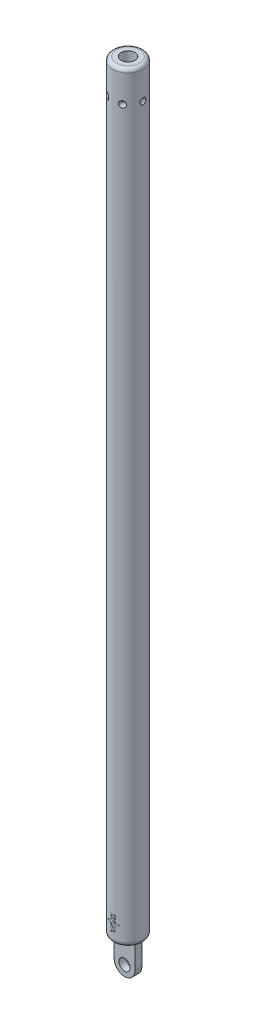
SolidWorks part; units mm, degrees
note: '?' marks a value the reader was unsure of.
material "PW100:Mi:0:3:C1:0:1:2:Re:26:"
ref_plane "Front" through (0, 0, 0) normal (0, 0, 1) x (1, 0, 0)
ref_plane "Top" through (0, 0, 0) normal (0, 1, 0) x (1, 0, 0)
ref_plane "Right" through (0, 0, 0) normal (1, 0, 0) x (0, 0, -1)
sketch "Support-Front" plane through (0, 0, 0) normal (0, 0, 1) x (1, 0, 0)
  line L0 (5, 545.5747) -> (-5, 545.5747)
  line L3 (11, 2.5396) -> (11, 550.5747)
  line L4 (11, 550.5747) -> (-11, 550.5747)
  line L10 (7.5, 1.7315) -> (-7.5, 1.7315)
  line L11 (11, 530.2768) -> (9.8163, 527.988) construction
  line L12 (9.0513, 0) -> (0, -2.4253)
  line L14 (-11, 2.5396) -> (-11, 550.5747)
  line L15 (5, 550.5747) -> (0, 545.5747) construction
  line L18 (7.5, 1.7315) -> (7.5, -17.4253)
  line L19 (0, 0) -> (11, 2.5396) construction
  line L20 (-9.0513, 0) -> (0, -2.4253)
  line L23 (5, 550.5747) -> (5, 50.5747)
  line L24 (-7.5, -17.4253) -> (-7.5, 1.7315)
  line L25 (11, 525.6993) -> (11, 530.2768)
  line L26 (9.8163, 527.988) -> (11, 527.988) construction
  line L29 (-5, 550.5747) -> (-5, 50.5747)
  line L30 (9.0513, 0) -> (-9.0513, 0)
  line L31 (-5, 50.5747) -> (5, 50.5747)
  line L35 (-11, 550.5747) -> (11, 527.988) construction
  line L36 (9.8163, 527.988) -> (11, 550.5747) construction
  line L37 (0, -24.9253) -> (0, 550.5747) construction
  line L44 (-5, 550.5747) -> (5, 550.5747) construction
  arc A0 (-11, 547.9456) -> (-8.3709, 550.5747) centre (-8.3709, 547.9456) cw
  arc A1 (11, 547.9456) -> (8.3709, 550.5747) centre (8.3709, 547.9456) ccw
  arc A3 (7.5, -17.4253) -> (-7.5, -17.4253) centre (0, -17.4253) cw
  arc A4 (9.0513, 0) -> (11, 2.5396) centre (8.3709, 2.5396) ccw
  arc A5 (-9.0513, 0) -> (-11, 2.5396) centre (-8.3709, 2.5396) cw
  circle A6 centre (0, -17.4253) radius 4.05
  arc A7 (11, 530.2768) -> (11, 525.6993) centre (12.6209, 527.988) ccw
  dimension "Diam-Hole-Clevis" = 8.1
  dimension "Diam-Piston-Rod" = 10
  dimension "D3" = 45.754
  dimension "D4" = 3
  dimension "D1" = 13
  dimension "Height-Clevis" = 15
  dimension "Diam-Cylinder" = 22
  dimension "Stroke" = 495
  dimension "D2" = 62.653
  dimension "D5" = 15
  dimension "Dist-End-Fitting-Cylinder" = 15
  dimension "D6" = 45
  dimension "Length-Cylinder" = 553
sketch "Support-Right" plane through (0, 0, 0) normal (1, 0, 0) x (0, 0, -1)
  line L1 (2.5, 1.7315) -> (-2.5, 1.7315)
  line L2 (2.5, 1.7315) -> (2.5, -24.9253)
  line L3 (2.5, -24.9253) -> (-2.5, -24.9253)
  line L4 (-2.5, 1.7315) -> (-2.5, -24.9253)
  dimension "Width-Clevis" = 5
ref_axis "Ref-Axis-Center" through (0, 550.5747, 0) along (0, -1, 0)?
ref_plane "Ref-Plane-Cylinder-Front" through (0, 550.5747, 0) normal (0, 1, 0) x (-1, 0, 0)
ref_plane "Ref-Plane-Front" through (0, 0, 0) normal (0, 0, 1) x (1, 0, 0)
ref_plane "Ref-Plane-Cylinder-End" through (0, 0, 0) normal (0, 1, 0) x (-1, 0, 0)
ref_plane "Ref-Plane-Clevis-Front" through (0, 0, -2.5) normal (0, 0, 1) x (1, 0, 0)
ref_plane "Ref-Plane-Clevis-End" through (0, 0, 2.5) normal (0, 0, 1) x (1, 0, 0)
ref_plane "Ref-Plane-Logo" through (0, 0, 22) normal (0, 0, 1) x (1, 0, 0)
sketch "Sketch5" plane through (0, 0, 0) normal (0, 0, 1) x (1, 0, 0)
  line L1 (-9.0513, 0) -> (0, -2.4253) construction
  line L2 (-5, 550.5747) -> (-5, 50.5747) construction
  line L3 (-5, 50.5747) -> (5, 50.5747) construction
  line L4 (11, 550.5747) -> (-11, 550.5747) construction
  line L5 (-5, 550.5747) -> (-5, 50.5747)
  line L6 (-5, 50.5747) -> (0, 50.5747)
  line L7 (-5, 550.5747) -> (-8.3709, 550.5747)
  line L8 (-9.0513, 0) -> (0, -2.4253)
  line L12 (-11, 2.5396) -> (-11, 550.5747) construction
  line L15 (0, -24.9253) -> (0, 550.5747) construction
  line L21 (-11, 2.5396) -> (-11, 547.9456)
  line L22 (0, -24.9253) -> (0, 550.5747) construction
  line L23 (0, -2.4253) -> (0, 50.5747)
  arc A0 (-8.3709, 550.5747) -> (-11, 547.9456) centre (-8.3709, 547.9456) ccw construction
  arc A1 (-8.3709, 550.5747) -> (-11, 547.9456) centre (-8.3709, 547.9456) ccw
  arc A2 (-11, 2.5396) -> (-9.0513, 0) centre (-8.3709, 2.5396) ccw construction
  arc A3 (-11, 2.5396) -> (-9.0513, 0) centre (-8.3709, 2.5396) ccw
revolve "Body" add sketch "Sketch5" angle 360 about L15
sketch "Sketch11" plane through (0, 0, 0) normal (0, 0, 1) x (1, 0, 0)
  line L1 (11, 525.6993) -> (11, 530.2768) construction
  line L2 (11, 527.988) -> (11, 530.2768)
  line L4 (9.8163, 527.988) -> (11, 527.988) construction
  line L6 (9.8163, 527.988) -> (12.6209, 527.988) construction
  line L7 (9.8163, 527.988) -> (11, 527.988)
  arc A0 (11, 530.2768) -> (11, 525.6993) centre (12.6209, 527.988) ccw construction
  arc A1 (11, 530.2768) -> (9.8163, 527.988) centre (12.6209, 527.988) ccw
revolve "Cut-Mark" cut sketch "Sketch11" angle 360 about L4
pattern_circular "Pattern-Mark" count 6 over 360 about axis through (0, 0, 0) along (0, 1, 0) of "Cut-Mark"
sketch "Sketch13" plane through (0, 0, -2.5) normal (0, 0, 1) x (1, 0, 0)
  line L0 (7.5, 1.7315) -> (7.5, -17.4253) construction
  line L1 (7.5, 1.7315) -> (-7.5, 1.7315) construction
  line L2 (-7.5, -17.4253) -> (-7.5, 1.7315) construction
  line L3 (7.5, 1.7315) -> (7.5, -17.4253)
  line L4 (7.5, 1.7315) -> (-7.5, 1.7315)
  line L5 (-7.5, -17.4253) -> (-7.5, 1.7315)
  arc A0 (-7.5, -17.4253) -> (7.5, -17.4253) centre (0, -17.4253) ccw construction
  arc A1 (-7.5, -17.4253) -> (7.5, -17.4253) centre (0, -17.4253) ccw
  circle A2 centre (0, -17.4253) radius 4.05 construction
  circle A3 centre (0, -17.4253) radius 4.05
extrude "Clevis" add sketch "Sketch13" along normal up to surface (5 mm away) up to plane "Ref-Plane-Clevis-End"
sketch "Sketch17" plane through (-0.6718, 2.9011, 22) normal (0, 0, 1) x (1, 0, 0)
  line L0 (0.8209, 8.1651) -> (2.1631, 8.1651)
  line L1 (0.79, 9.6233) -> (1.4113, 10.2287)
  line L2 (3.2638, 9.6992) -> (3.2673, 10.445)
  line L3 (1.0074, 10.6773) -> (1.0052, 10.6752)
  line L4 (1.0052, 10.6752) -> (0.3932, 10.0994)
  line L5 (-1.803, 10.4733) -> (-1.8065, 9.7276)
  line L6 (3.612, 9.7429) -> (5.0038, 9.7429)
  line L7 (5.0038, 9.7429) -> (5.0038, 10.3892)
  line L8 (5.0038, 10.3892) -> (3.612, 10.3892)
  line L9 (3.612, 10.3892) -> (3.612, 9.7429)
  line L10 (-2.1542, 10.4222) -> (-3.5461, 10.4222)
  line L11 (-3.5461, 10.4222) -> (-3.5461, 9.776)
  line L12 (-3.5461, 9.776) -> (-2.1542, 9.776)
  line L13 (-2.1542, 9.776) -> (-2.1542, 10.4222)
  line L14 (2.693, 13.5884) -> (-0.2002, 13.5884)
  line L15 (-0.2002, 11.4012) -> (2.6829, 11.4012)
  line L16 (2.6829, 11.4012) -> (2.6829, 11.8983)
  line L17 (2.6829, 11.8983) -> (-0.2444, 11.8983)
  line L18 (-0.2444, 13.0913) -> (2.6907, 13.0913)
  line L19 (2.6907, 13.0913) -> (2.693, 13.5884)
  line L20 (0.9163, 15.6852) -> (0.2287, 14.8104)
  line L21 (-0.435, 16.0748) -> (-1.0812, 16.0778)
  line L22 (0.669, 14.4533) -> (1.3566, 15.328)
  line L23 (2.042, 14.2241) -> (2.5888, 14.2215)
  line L24 (0.8191, 7.7674) -> (0.8209, 8.1651)
  line L25 (-1.3165, 8.6721) -> (-1.3165, 8.175)
  line L26 (-1.3165, 8.175) -> (0.3736, 8.175)
  line L27 (0.3736, 8.175) -> (0.3736, 7.7276)
  line L28 (2.6602, 7.7276) -> (2.6602, 8.6721)
  line L29 (2.6602, 8.6721) -> (-1.3165, 8.6721)
  line L30 (2.1631, 8.1651) -> (2.1612, 7.7612)
  line L31 (-0.2877, 4.9018) -> (-1.3328, 4.6457)
  line L32 (-1.3328, 4.6457) -> (-1.3354, 4.0989)
  line L33 (-1.3354, 4.0989) -> (2.6462, 5.1244)
  line L34 (2.6462, 5.1244) -> (2.6492, 5.7706)
  line L35 (2.6492, 5.7706) -> (-1.3225, 6.8826)
  line L36 (-1.3225, 6.8826) -> (-1.325, 6.3358)
  line L37 (-1.325, 6.3358) -> (-0.2824, 6.0541)
  line L38 (-0.2824, 6.0541) -> (-0.2877, 4.9018)
  line L39 (1.9517, 5.4507) -> (0.2099, 5.0238)
  line L40 (0.2099, 5.0238) -> (0.2141, 5.92)
  line L41 (0.2141, 5.92) -> (1.9517, 5.4507)
  line L42 (0.6718, 8.6721) -> (0.6718, 4.0989) construction
  line L43 (0.6718, 4.0989) -> (-1.3354, 4.0989) construction
  line L44 (0.6718, 4.0989) -> (0.6718, -2.9011) construction
  arc A0 (-0.2002, 13.5884) -> (-0.2002, 11.4012) centre (-0.2002, 12.4948) ccw
  arc A1 (-0.2444, 13.0913) -> (-0.2444, 11.8983) centre (-0.2444, 12.4948) ccw
  arc A2 (-1.8065, 9.7276) -> (0.79, 9.6233) centre (-0.4589, 10.9051) ccw
  arc A3 (1.9329, 10.3856) -> (1.4113, 10.2287) centre (1.8227, 9.8064) ccw
  arc A4 (3.2638, 9.6992) -> (1.9329, 10.3856) centre (1.4406, 7.7974) ccw
  arc A5 (3.2673, 10.445) -> (2.0649, 10.9746) centre (1.391, 7.8145) ccw
  arc A6 (2.0649, 10.9746) -> (1.0074, 10.6773) centre (1.8227, 9.8064) ccw
  arc A7 (-0.9149, 9.8486) -> (0.3932, 10.0994) centre (-0.4584, 11.0045) ccw
  arc A8 (-1.803, 10.4733) -> (-0.9149, 9.8486) centre (-0.0651, 12.0004) ccw
  arc A9 (0.3736, 7.7276) -> (0.9229, 6.9022) centre (1.2684, 7.7276) ccw
  arc A10 (0.9229, 6.9022) -> (2.1109, 6.9022) centre (1.5169, 8.3215) ccw
  arc A11 (2.6921, 15.0622) -> (0.9163, 15.6852) centre (1.6979, 15.0707) ccw
  arc A12 (-0.8145, 15.3405) -> (0.2287, 14.8104) centre (-0.2403, 15.1791) ccw
  arc A13 (-0.435, 16.0748) -> (-0.8145, 15.3405) centre (1.1577, 14.7863) ccw
  arc A14 (-1.0812, 16.0778) -> (-1.2815, 15.2084) centre (1.6199, 14.9976) ccw
  arc A15 (-1.2815, 15.2084) -> (0.669, 14.4533) centre (-0.1908, 15.1292) ccw
  arc A16 (2.2431, 15.0576) -> (1.3566, 15.328) centre (1.7474, 15.0208) ccw
  arc A17 (2.042, 14.2241) -> (2.2431, 15.0576) centre (0.8453, 14.9539) ccw
  arc A18 (2.5888, 14.2215) -> (2.6921, 15.0622) centre (-1.0399, 15.0941) ccw
  arc A19 (2.1109, 6.9022) -> (2.6602, 7.7276) centre (1.7654, 7.7276) ccw
  arc A20 (0.8191, 7.7674) -> (1.0751, 7.361) centre (1.2665, 7.7654) ccw
  arc A21 (1.0751, 7.361) -> (1.9015, 7.3572) centre (1.4924, 8.2428) ccw
  arc A22 (1.9015, 7.3572) -> (2.1612, 7.7612) centre (1.7139, 7.7633) ccw
  point P87 (5.0038, 10.066)
extrude "Cut-Logo" cut sketch "Sketch17" against normal offset from surface (11.3847 mm away) 0.1
ref_axis "Ref-Axis-End-Fitting" through (0, -17.4253, 27.5862) along (0, 0, -1)?
ref_plane "Ref-Plane-End-Fitting" through (0, -17.4253, 0) normal (0, 1, 0) x (-1, 0, 0)
equation "\"Thickness-Plate-Thread@Support-Front\" = \"Length-Thread@Support-Front\" / 5"
equation "\"Pitch@Thread-Simple\" = \"Pitch-Thread@Support-Thread\""
equation "\"Width-Thread-Bottom@Support-Thread\" = \"Pitch-Thread@Support-Thread\" / 4"
equation "\"Width-Thread-Top@Support-Thread\" = \"Pitch-Thread@Support-Thread\" / 8"
equation "\"Pitch@Thread-Simple\" = \"Pitch-Thread@Support-Thread\" "
equation "\"Num-Thread@Thread-Simple\" = INT(\"Length-Thread@Support-Front\" / \"Pitch-Thread@Support-Thread\" +1)"
equation "\"Dist@Ref-Plane-Logo\" = \"Diam-Cylinder@Support-Front\""
